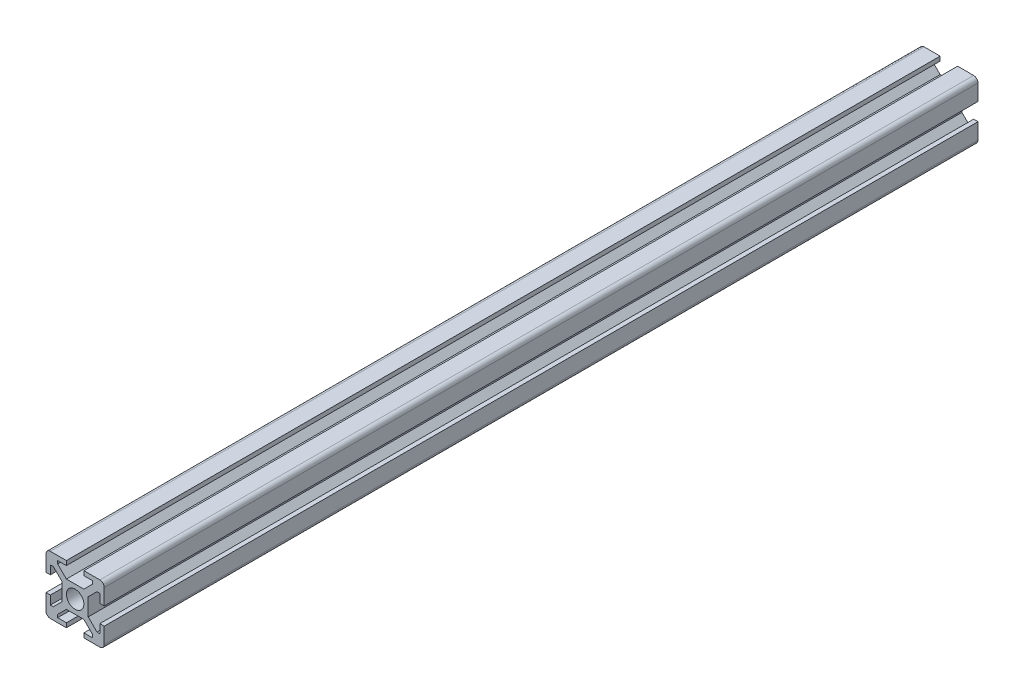
SolidWorks part; units mm, degrees
ref_plane "Plan de face" through (0, 0, 0) normal (0, 0, 1) x (1, 0, 0)
ref_plane "Plan de dessus" through (0, 0, 0) normal (0, 1, 0) x (1, 0, 0)
ref_plane "Plan de droite" through (0, 0, 0) normal (1, 0, 0) x (0, 0, -1)
sketch "Esquisse1" plane through (0, 0, 0) normal (0, 0, 1) x (1, 0, 0)
  line L0 (-10, 10) -> (10, -10) construction
  line L1 (-10, 10) -> (10, 10)
  line L2 (-10, 10) -> (-10, -10)
  line L3 (-10, -10) -> (10, -10)
  line L4 (10, 10) -> (10, -10)
  dimension "D1" = 20
extrude "Extrusion1" add sketch "Esquisse1" along normal mid plane 300
fillet "Congé1" radius 1.5 4 edges at (-10, -10, 0) (10, -10, 0) (-10, 10, 0) (10, 10, 0)
sketch "Esquisse2" plane through (0, 0, -150) normal (0, 0, -1) x (-1, 0, 0)
  line L0 (-10, 3) -> (-10, -3)
  line L1 (-10, -8.5) -> (-10, 8.5) construction
  line L2 (-10, -3) -> (-8.5, -3)
  line L3 (-8.5, -3) -> (-8.5, -6)
  line L4 (-8.5, 6) -> (-7.5, 6)
  line L5 (-4.5, -3) -> (-4.5, 3)
  line L6 (-7.5, 6) -> (-4.5, 3)
  line L7 (-8.5, 6) -> (-8.5, 3)
  line L8 (-8.5, 3) -> (-10, 3)
  line L9 (0, 0) -> (-10, 0) construction
  line L10 (-8.5, -6) -> (-7.5, -6)
  line L11 (-7.5, -6) -> (-4.5, -3)
  point P4 (-10, 0)
  dimension "D1" = 6
  dimension "D2" = 12
  dimension "D3" = 1.5
  dimension "D4" = 5.5
  dimension "D5" = 135
extrude "Enlèv. mat.-Extru.1" cut sketch "Esquisse2" against normal through all
ref_axis "Axe1" through (0, 0, 9.3338) along (0, 0, -1)
pattern_circular "Répétition circulaire1" count 4 over 360 about axis through (0, 0, 9.3338) along (0, 0, -1) of "Enlèv. mat.-Extru.1"
hole_wizard "Trou taraudé M6x1.01" positions "Esquisse4" profile "Esquisse5" tap size "M6x1.0" standard "Ansi Métrique"
sketch "Esquisse4" plane through (0, 0, -150) normal (0, 0, -1) x (-1, 0, 0)
  point P0 (0, 0)
sketch "Esquisse5" plane through (0, 0, -150) normal (1, 0, 0) x (0, 1, 0)
  line L0 (0, 0) -> (0, 31.5022)
  line L1 (0, 31.5022) -> (2.5, 30)
  line L2 (2.5, 30) -> (2.5, 24)
  line L3 (2.5, 24) -> (3, 24)
  line L4 (3, 24) -> (3, 0)
  line L5 (3, 0) -> (0, 0)
  line L10 (0, 31.5022) -> (-2.5, 30) construction
  line L11 (0, -6.35) -> (0, 107.95) construction
  dimension "Diamètre du trou pour taraudage" = 5
  dimension "Profondeur du trou pour taraudage" = 30
  dimension "Diamètre principal du filetage" = 6
  dimension "Profondeur du filetage" = 24
  dimension "Angle de pointe" = 118
mirror "Symétrie1" about plane through (0, 0, 0) normal (0, 0, 1) of "Trou taraudé M6x1.01"
equation "\"D1@Extrusion1\"= \"lon\""
